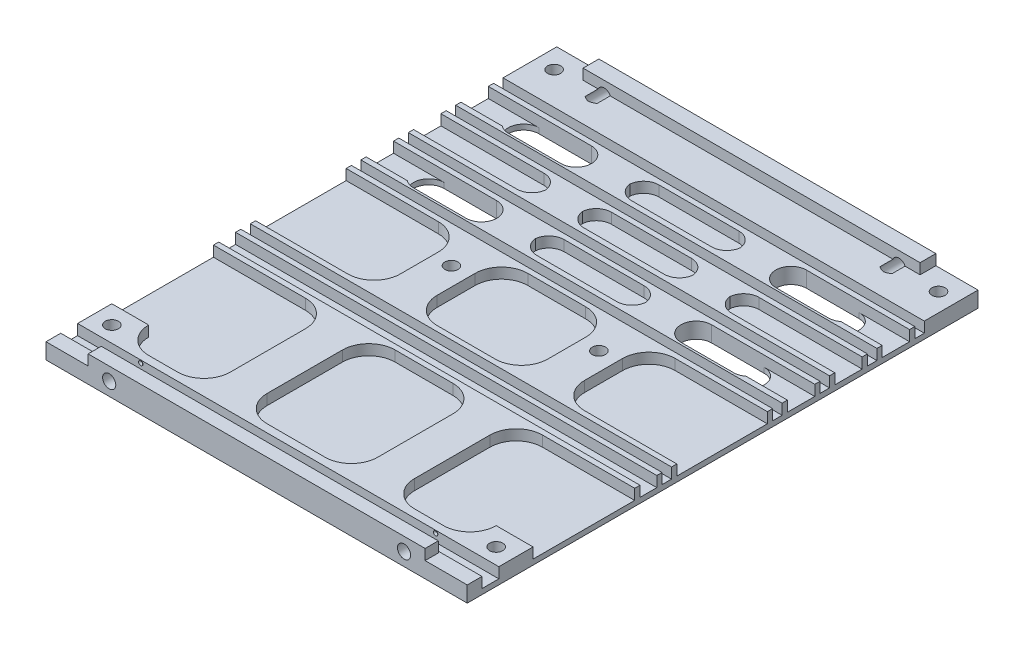
SolidWorks part; units mm, degrees
material "6061-T6 (SS)"
ref_plane "Front Plane" through (0, 0, 0) normal (0, 0, 1) x (1, 0, 0)
ref_plane "Top Plane" through (0, 0, 0) normal (0, 1, 0) x (1, 0, 0)
ref_plane "Right Plane" through (0, 0, 0) normal (1, 0, 0) x (0, 0, -1)
sketch "Sketch1" plane through (0, 0, 0) normal (0, 1, 0) x (1, 0, 0)
  line L0 (-28, 47) -> (28, 47) construction
  line L1 (-40, -48.5) -> (40, -48.5)
  line L2 (-40, -48.5) -> (-40, 48.5)
  line L3 (-40, 48.5) -> (40, 48.5)
  line L4 (40, -48.5) -> (40, 48.5)
  line L5 (-40, -48.5) -> (40, 48.5) construction
  line L6 (-40, 48.5) -> (40, -48.5) construction
  line L7 (28, 47) -> (28, -47) construction
  line L8 (28, -47) -> (-28, -47) construction
  line L9 (-28, -47) -> (-28, 47) construction
  line L10 (-40, 0) -> (-28, 0) construction
  line L12 (0, 47) -> (0, 48.5) construction
  circle A0 centre (-28, 47) radius 1.75
  circle A1 centre (28, 47) radius 1.75
  circle A2 centre (28, -47) radius 1.75
  circle A3 centre (-28, -47) radius 1.75
  point P0 (0, 0)
  dimension "D5" = 3.5
  dimension "D1" = 80
  dimension "D2" = 97
  dimension "D3" = 56
  dimension "D4" = 94
extrude "Boss-Extrude1" add sketch "Sketch1" along normal blind 1 contours L1 L4 L3 L2 A3 A2 A1 A0 | A0 | A1 | A2 | A3 | L2 L1 L4 L3 region at (0, 0, 0) region at (-28, 0, 46.9476) region at (-28, 0, -46.9476) region at (28, 0, 46.9476) region at (28, 0, -46.9476)
sketch "Sketch4" plane through (0, 1, 0) normal (0, 1, 0) x (1, 0, 0)
  line L1 (-40, 39.3) -> (40, 39.3)
  line L2 (-40, 39.3) -> (-40, 38.3)
  line L3 (-40, 38.3) -> (40, 38.3)
  line L4 (40, 39.3) -> (40, 38.3)
  line L6 (-40, 48.5) -> (40, 48.5) construction
  line L7 (-40, 36.5) -> (40, 36.5)
  line L8 (-40, 36.5) -> (-40, 35.5)
  line L9 (-40, 35.5) -> (40, 35.5)
  line L10 (40, 36.5) -> (40, 35.5)
  line L11 (-40, 38.3) -> (-40, 37.4) construction
  line L12 (-40, 37.4) -> (-40, 36.5) construction
  line L13 (-40, 37.4) -> (40, 37.4) construction
  line L14 (-28, 48.5) -> (-28, 37.4) construction
  line L15 (-40, -48.5) -> (-40, 48.5) construction
  line L16 (40, -48.5) -> (40, 48.5) construction
  dimension "D1" = 1
  dimension "D2" = 1.8
  dimension "D3" = 12
  dimension "D4" = 11.1
extrude "Boss-Extrude2" add sketch "Sketch4" along normal blind 2
pattern_linear "LPattern1" count 4 spacing 9 along (0, 0, 1) of "Boss-Extrude2"
ref_plane "Plane1" through (0, 0, -37.4) normal (0, 0, 1) x (1, 0, 0)
ref_plane "Plane2" through (0, 0, 0.1) normal (0, 0, 1) x (1, 0, 0)
mirror "Mirror1" about plane through (0, 0, 0.1) normal (0, 0, 1) of "LPattern1"
sketch "Sketch10" plane through (0, 1, 0) normal (0, 1, 0) x (1, 0, 0)
  line L0 (40, -39.5) -> (-40, -39.5) construction
  line L1 (-40, -17.7) -> (40, -17.7)
  line L2 (-40, -17.7) -> (-40, -39.5)
  line L3 (-40, -39.5) -> (40, -39.5)
  line L4 (40, -17.7) -> (40, -39.5)
  line L5 (40, -48.5) -> (40, -39.5) construction
extrude "Remove_3_rows" cut sketch "Sketch10" along normal through all
sketch "Sketch5" plane through (0, 1, 0) normal (0, -1, 0) x (1, 0, 0)
  line L0 (36.5, -44.5) -> (-36.5, -44.5) construction
  line L1 (-36.5, -44.5) -> (-36.5, 39.5) construction
  line L2 (-36.5, 39.5) -> (36.5, 39.5) construction
  line L3 (36.5, 39.5) -> (36.5, -44.5) construction
  line L4 (0, -44.5) -> (0, 0) construction
  line L5 (0, 0) -> (36.5, 0) construction
  line L6 (-36.5, -44.5) -> (-36.5, -48.5) construction
  line L7 (-40, -48.5) -> (40, -48.5) construction
  line L8 (-14, -2.5) -> (14, -2.5) construction
  line L9 (-14, -2.5) -> (-14, -44.5) construction
  line L10 (-14, -2.5) -> (-14, 39.5) construction
  point P3 (-36.5, 39.5)
  point P5 (36.5, 39.5)
  point P7 (36.5, -44.5)
  point P18 (-36.5, -44.5)
  point P20 (0, -2.5)
  point P24 (-14, -2.5)
  point P25 (14, -2.5)
  dimension "D1" = 28
  dimension "D2" = 73
  dimension "D3" = 84
  dimension "D4" = 4
sketch "Sketch12" plane through (0, 1, 0) normal (0, 1, 0) x (1, 0, 0)
  line L4 (-40, -14.1) -> (40, -14.1) construction
  line L5 (40, -14.1) -> (40, -44.1) construction
  line L6 (40, -44.1) -> (-40, -44.1) construction
  line L7 (-40, -12.5) -> (-40, -14.1) construction
  line L8 (-40, -11.5) -> (40, -11.5)
  line L9 (-40, -11.5) -> (-40, -12.5)
  line L10 (-40, -12.5) -> (40, -12.5)
  line L11 (40, -11.5) -> (40, -12.5)
  line L12 (40, -16.7) -> (-40, -16.7)
  line L13 (40, -16.7) -> (40, -15.7)
  line L14 (40, -15.7) -> (-40, -15.7)
  line L15 (-40, -16.7) -> (-40, -15.7)
  line L16 (-40, -14.1) -> (-40, -15.7) construction
  line L17 (-40, -42.5) -> (-40, -44.1) construction
  line L18 (-40, -41) -> (40, -41)
  line L19 (-40, -41) -> (-40, -42.5)
  line L20 (-40, -42.5) -> (40, -42.5)
  line L21 (40, -41) -> (40, -42.5)
  line L22 (40, -45.7) -> (-40, -45.7)
  line L23 (40, -45.7) -> (40, -47.2)
  line L24 (40, -47.2) -> (-40, -47.2)
  line L25 (-40, -45.7) -> (-40, -47.2)
  line L26 (-40, -44.1) -> (-40, -45.7) construction
  line L27 (-40, -11.5) -> (40, -11.5) construction
  line L28 (40, -48.5) -> (40, -12.5) construction
  line L30 (-40, -48.5) -> (-40, -12.5) construction
  dimension "D2" = 33.2
  dimension "D3" = 3.2
  dimension "D4" = 1
  dimension "D6" = 3.2
  dimension "D7" = 1.5
extrude "PayloadSlots" add sketch "Sketch12" along normal up to surface (2 mm away) up to face at (0, 3, 9.2)
sketch "Sketch16" plane through (0, 1, 0) normal (0, 1, 0) x (1, 0, 0)
  line L0 (-14, 2.5) -> (14, 2.5) construction
  line L1 (-14, 2.5) -> (14, 2.5)
  line L2 (-17.5, 2.5) -> (-17.5, -8.7)
  line L4 (-17.5, -8.7) -> (-10.5, -8.7)
  line L5 (-10.5, -8.7) -> (-10.5, 2.5)
  line L6 (10.5, 2.5) -> (10.5, -8.7)
  line L7 (10.5, -8.7) -> (17.5, -8.7)
  line L8 (17.5, -8.7) -> (17.5, 2.5)
  line L9 (-40, -8.7) -> (40, -8.7) construction
  circle A0 centre (-14, 2.5) radius 3.5
  circle A1 centre (14, 2.5) radius 3.5
  dimension "D1" = 7
  dimension "D2" = 7
extrude "Boss-Extrude8" add sketch "Sketch16" along normal up to surface (2 mm away) contours A0 | A0 L2 L5 | A1 L6 L8 | A1 region at (14, 1, -5.901) region at (14, 1, 4.4383) region at (-14, 1, 0.901) region at (-14, 1, 4.4383) up to face at (0, 3, 9.2)
sketch "Sketch22" plane through (0, 1, 0) normal (0, 1, 0) x (1, 0, 0)
  line L0 (-40, -48.5) -> (-40, -47.2) construction
  line L1 (-40, 48.5) -> (40, 48.5)
  line L2 (-40, 48.5) -> (-40, 39.3)
  line L3 (-40, 39.3) -> (40, 39.3)
  line L4 (40, 48.5) -> (40, 39.3)
  line L5 (40, -48.5) -> (-40, -48.5)
  line L6 (40, -48.5) -> (40, -46)
  line L7 (40, -46) -> (-40, -46)
  line L8 (-40, -48.5) -> (-40, -46)
  dimension "D1" = 2.5
extrude "Boss-Extrude9" add sketch "Sketch22" along normal blind 4
fillet "Fillet4" radius 5 4 edges at (-10.5, 2, 8.7) (-17.5, 2, 8.7) (10.5, 2, 8.7) (17.5, 2, 8.7)
sketch "Sketch23" plane through (0, 0, -48.5) normal (0, 0, -1) x (-1, 0, 0)
  line L0 (-28, 2.5) -> (28, 2.5) construction
  line L1 (28, 2.5) -> (40, 2.5) construction
  line L2 (-28, 2.5) -> (-40, 2.5) construction
  line L3 (40, 5) -> (40, 0) construction
  line L4 (-40, 5) -> (-40, 0) construction
  dimension "D1" = 2.5
  dimension "D2" = 56
ref_plane "Plane3" through (0, 0, 0) normal (0, 0, -1) x (-1, 0, 0)
hole_wizard "M3x0.5 Tapped Hole2" positions "Sketch24" profile "Sketch25" tap size "M3x0.5" standard "ANSI Metric"
sketch "Sketch24" plane through (0, 0, -48.5) normal (0, 0, -1) x (-1, 0, 0)
  point P0 (-28, 2.5)
  point P3 (28, 2.5)
sketch "Sketch25" plane through (28, 2.5, -48.5) normal (1, 0, 0) x (0, 1, 0)
  line L0 (0, 0) -> (0, 6.2511)
  line L1 (0, 6.2511) -> (1.25, 5.5)
  line L2 (1.25, 5.5) -> (1.25, 0)
  line L5 (1.25, 0) -> (0, 0)
  line L10 (0, 6.2511) -> (-1.25, 5.5) construction
  line L11 (0, -6.35) -> (0, 107.95) construction
  dimension "Tap Drill Dia." = 2.5
  dimension "Tap Drill Depth" = 5.5
  dimension "Drill Angle" = 118
cosmetic thread "Hole Thread7" parameters "D1"=5.1, "D2"=3
cosmetic thread "Hole Thread8" parameters "D1"=5.1, "D2"=3
mirror "Mirror2" about plane through (0, 0, 0) normal (0, 0, -1) of "M3x0.5 Tapped Hole2"
sketch "Sketch26" plane through (0, 5, 0) normal (0, 1, 0) x (1, 0, 0)
  line L0 (-40, 48.5) -> (-40, 39.3) construction
  line L1 (40, 39.3) -> (-40, 39.3)
  line L2 (40, 39.3) -> (40, 45.5)
  line L3 (40, 45.5) -> (-40, 45.5)
  line L4 (-40, 39.3) -> (-40, 45.5)
  line L5 (-28, 48.5) -> (-40, 48.5) construction
  line L6 (40, -48.5) -> (40, -46) construction
  line L7 (-40, -46) -> (40, -46)
  line L8 (-40, -46) -> (-40, -45.5)
  line L9 (-40, -45.5) -> (40, -45.5)
  line L10 (40, -46) -> (40, -45.5)
  line L11 (-40, -48.5) -> (40, -48.5) construction
  line L12 (40, 48.5) -> (-40, 48.5) construction
  line L13 (-40, -48.5) -> (-32, -48.5)
  line L14 (-40, -48.5) -> (-40, -45.5)
  line L15 (-40, -45.5) -> (-32, -45.5)
  line L16 (-32, -48.5) -> (-32, -45.5)
  line L17 (40, -48.5) -> (32, -48.5)
  line L18 (40, -48.5) -> (40, -45.5)
  line L19 (40, -45.5) -> (32, -45.5)
  line L20 (32, -48.5) -> (32, -45.5)
  line L21 (40, 45.5) -> (32, 45.5)
  line L22 (40, 45.5) -> (40, 48.5)
  line L23 (40, 48.5) -> (32, 48.5)
  line L24 (32, 45.5) -> (32, 48.5)
  line L25 (-32, 45.5) -> (-32, -45.5) construction
  line L26 (-40, 45.5) -> (-32, 45.5)
  line L27 (-40, 45.5) -> (-40, 48.5)
  line L28 (-40, 48.5) -> (-32, 48.5)
  line L29 (-32, 45.5) -> (-32, 48.5)
  line L30 (32, -45.5) -> (32, 45.5) construction
  line M16 (-40, 48.5) -> (-40, 39.3)
  line M17 (-40, 39.3) -> (40, 39.3)
  line M18 (40, 39.3) -> (40, 48.5)
  line M19 (40, 48.5) -> (-40, 48.5)
  dimension "D1" = 3
  dimension "D2" = 3
  dimension "D3" = 8
  dimension "D4" = 8
extrude "Cut-Extrude1" cut sketch "Sketch26" against normal up to surface (2 mm away) contours L10 L7 L8 L9 | L13 L16 L9 L14 | L20 L17 L18 L9 | L24 L3 M18 M19 | L3 M18 M16 M17 | L3 L29 M19 M16 region at (0, 5, -42.4) region at (36, 5, -47) region at (-36, 5, -47) region at (-36, 5, 47.25) region at (36, 5, 47.25) up to face at (0, 3, -38.8)
sketch "Sketch28" plane through (0, 1, 0) normal (0, 1, 0) x (1, 0, 0)
  line L0 (-40, 35.5) -> (40, 35.5) construction
  line L1 (-17.5, 35.5) -> (-10.5, 35.5)
  line L2 (-17.5, 35.5) -> (-17.5, -41)
  line L3 (-17.5, -41) -> (-10.5, -41)
  line L4 (-10.5, 35.5) -> (-10.5, -41)
  line L5 (40, -41) -> (-40, -41) construction
  line L6 (-40, -41) -> (-17.5, -41) construction
  line L7 (10.5, -41) -> (17.5, -41)
  line L8 (10.5, -41) -> (10.5, 35.5)
  line L9 (10.5, 35.5) -> (17.5, 35.5)
  line L10 (17.5, -41) -> (17.5, 35.5)
  line L11 (-10.5, -41) -> (10.5, -41) construction
  line L12 (40, -41) -> (17.5, -41) construction
  line L13 (-40, -16.7) -> (40, -16.7) construction
  line L14 (40, 21.3) -> (-40, 21.3) construction
  line L15 (40, 12.3) -> (-40, 12.3) construction
  line L16 (-40, 8.5) -> (40, 8.5) construction
  line L17 (-40, 17.5) -> (40, 17.5) construction
  line L18 (-40, 26.5) -> (40, 26.5) construction
  line L19 (40, 30.3) -> (-40, 30.3) construction
  line L20 (-40, -16.7) -> (40, -16.7)
  line L21 (40, 21.3) -> (-40, 21.3)
  line L22 (40, 12.3) -> (-40, 12.3)
  line L23 (-40, 8.5) -> (40, 8.5)
  line L24 (-40, 17.5) -> (40, 17.5)
  line L25 (-40, 26.5) -> (40, 26.5)
  line L26 (40, 30.3) -> (-40, 30.3)
  line L27 (-7.9, 14.9) -> (-7.9, 35.5) construction
  line L29 (7.9, 14.9) -> (7.9, 35.5) construction
  arc A0 (-10.5, 2.5) -> (-17.5, 2.5) centre (-14, 2.5) ccw construction
  arc A1 (-10.5, 2.5) -> (-17.5, 2.5) centre (-14, 2.5) ccw
  arc A2 (17.5, 2.5) -> (10.5, 2.5) centre (14, 2.5) ccw construction
  arc A3 (17.5, 2.5) -> (10.5, 2.5) centre (14, 2.5) ccw
  circle A4 centre (-7.9, 14.9) radius 2.6
  circle A5 centre (7.9, 14.9) radius 2.6
  circle A6 centre (-7.9, 27.8487) radius 2.6
  circle A7 centre (7.9, 27.8487) radius 2.6
  circle A8 centre (-7.9, 37.2035) radius 2.6
  circle A9 centre (7.9, 36.6874) radius 2.6
  circle A10 centre (-21.1091, 18.5) radius 3.6091
  circle A11 centre (-21.1091, 27.8487) radius 3.6091
  circle A12 centre (-22.4679, 37.2035) radius 4.9679
  line M13 (-40, -41) -> (40, -41)
  line M15 (40, -16.7) -> (-40, -16.7)
  dimension "D1" = 21
  dimension "D2" = 7
extrude "Boss-Extrude10" add sketch "Sketch28" along normal up to surface (2 mm away) contours L4 L2 M15 M13 | A1 L4 L23 L2 | L25 L8 L21 L10 | L26 L10 L9 L8 | L24 L2 L22 L4 | L25 L2 L21 L4 | L26 L4 L1 L2 | A3 L10 L23 L8 | L10 L8 M13 M15 | L24 L8 L22 L10 region at (-14, 1, -32.9) region at (-14, 1, -23.9) region at (-14, 1, -14.9) region at (14, 1, -23.9) region at (14, 1, -14.9) region at (14, 1, -32.9) region at (-14, 1, -6.7806) region at (14, 1, -6.7806) region at (-14, 1, 28.85) region at (14, 1, 28.85) up to face at (-0.0114, 3, -44.6693)
fillet "Fillet5" radius 5 12 edges at (-17.5, 2, -8.5) (10.5, 2, -8.5) (17.5, 2, -8.5) (-10.5, 2, -8.5) (17.5, 2, 16.7) (17.5, 2, 41) (-17.5, 2, 41) (10.5, 2, 41) (10.5, 2, 16.7) (-17.5, 2, 16.7) (-10.5, 2, 16.7) (-10.5, 2, 41)
fillet "Fillet6" radius 2.9 24 edges at (-10.5, 2, -17.5) (17.5, 2, -17.5) (17.5, 2, -26.5) (-10.5, 2, -26.5) (-10.5, 2, -35.5) (17.5, 2, -35.5) (17.5, 2, -30.3) (-10.5, 2, -30.3) (-10.5, 2, -21.3) (17.5, 2, -21.3) (17.5, 2, -12.3) (-10.5, 2, -12.3) (-17.5, 2, -12.3) (10.5, 2, -12.3) (-17.5, 2, -21.3) (10.5, 2, -21.3) (10.5, 2, -30.3) (10.5, 2, -17.5) (10.5, 2, -26.5) (10.5, 2, -35.5) (-17.5, 2, -17.5) (-17.5, 2, -26.5) (-17.5, 2, -35.5) (-17.5, 2, -30.3)
sketch "Sketch29" plane through (0, 1, 0) normal (0, 1, 0) x (1, 0, 0)
  line L0 (40, -41) -> (22.5, -41) construction
  line L1 (33, -41) -> (40, -41)
  line L2 (33, -41) -> (33, -36)
  line L3 (33, -36) -> (40, -36)
  line L4 (40, -41) -> (40, -36)
  line L5 (40, -41) -> (40, -16.7) construction
  line L6 (-33, -36) -> (33, -36) construction
  line L7 (-40, -41) -> (-33, -41)
  line L8 (-40, -41) -> (-40, -36)
  line L9 (-40, -36) -> (-33, -36)
  line L10 (-33, -41) -> (-33, -36)
  dimension "D1" = 5
  dimension "D2" = 7
extrude "Boss-Extrude11" add sketch "Sketch29" along normal up to surface (2 mm away) up to face at (0, 3, 28.85)
fillet "Fillet7" radius 5 2 edges at (33, 2, 41) (-33, 2, 41)
hole_wizard "M3x0.5 Tapped Hole1" positions "Sketch20" profile "Sketch21" tap size "M3x0.5" standard "ANSI Metric" end condition up to next
sketch "Sketch20" plane through (0, 0, 0) normal (0, -1, 0) x (-1, 0, 0)
  point P0 (36.5, 44.5)
  point P3 (-36.5, 44.5)
  point P6 (14, 2.5)
  point P9 (-14, 2.5)
  point P12 (36.5, -39.5)
  point P15 (-36.5, -39.5)
sketch "Sketch21" plane through (-36.5, 0, -44.5) normal (1, 0, 0) x (0, 0, -1)
  line L0 (0, 0) -> (0, 3)
  line L1 (0, 3) -> (1.25, 3)
  line L2 (1.25, 3) -> (1.25, 0)
  line L5 (1.25, 0) -> (0, 0)
  line L11 (0, -6.35) -> (0, 107.95) construction
  dimension "Thru Tap Drill Dia." = 2.5
  dimension "Thru Tap Drill Depth" = 3
cosmetic thread "Hole Thread1" parameters "D2"=3
cosmetic thread "Hole Thread2" parameters "D2"=3
cosmetic thread "Hole Thread3" parameters "D2"=3
cosmetic thread "Hole Thread4" parameters "D2"=3
cosmetic thread "Hole Thread5" parameters "D2"=3
cosmetic thread "Hole Thread6" parameters "D2"=3
sketch "Sketch30" plane through (0, 1, 0) normal (0, 1, 0) x (1, 0, 0)
  line L0 (20.4, 14.6) -> (30.4, 14.6) construction
  line L1 (20.4, 17.5) -> (30.4, 17.5)
  line L2 (20.4, 11.7) -> (30.4, 11.7)
  line L3 (20.4, 32.6) -> (30.4, 32.6) construction
  line L4 (20.4, 35.5) -> (30.4, 35.5)
  line L5 (20.4, 29.7) -> (30.4, 29.7)
  line L6 (0, 0) -> (0, 48.9466) construction
  line L7 (-20.4, 32.6) -> (-30.4, 32.6) construction
  line L8 (-20.4, 35.5) -> (-30.4, 35.5)
  line L9 (-20.4, 29.7) -> (-30.4, 29.7)
  line L10 (-20.4, 14.6) -> (-30.4, 14.6) construction
  line L11 (-20.4, 17.5) -> (-30.4, 17.5)
  line L12 (-20.4, 11.7) -> (-30.4, 11.7)
  arc A2 (20.4, 17.5) -> (20.4, 11.7) centre (20.4, 14.6) ccw
  arc A3 (30.4, 11.7) -> (30.4, 17.5) centre (30.4, 14.6) ccw
  arc A4 (20.4, 35.5) -> (20.4, 29.7) centre (20.4, 32.6) ccw
  arc A5 (30.4, 29.7) -> (30.4, 35.5) centre (30.4, 32.6) ccw
  arc A6 (20.4, 35.5) -> (17.5156, 32.9) centre (20.4, 32.6) ccw construction
  arc A7 (20.4, 17.5) -> (17.5156, 14.9) centre (20.4, 14.6) ccw construction
  arc A8 (-20.4, 35.5) -> (-20.4, 29.7) centre (-20.4, 32.6) cw
  arc A9 (-30.4, 29.7) -> (-30.4, 35.5) centre (-30.4, 32.6) cw
  arc A10 (-20.4, 17.5) -> (-20.4, 11.7) centre (-20.4, 14.6) cw
  arc A11 (-30.4, 11.7) -> (-30.4, 17.5) centre (-30.4, 14.6) cw
  point P4 (25.4, 14.6)
  point P12 (25.4, 32.6)
  point P20 (-25.4, 32.6)
  point P34 (-25.4, 14.6)
  dimension "D1" = 10
  dimension "D2" = 10
extrude "Cut-Extrude2" cut sketch "Sketch30" against normal through all and the other way through all
